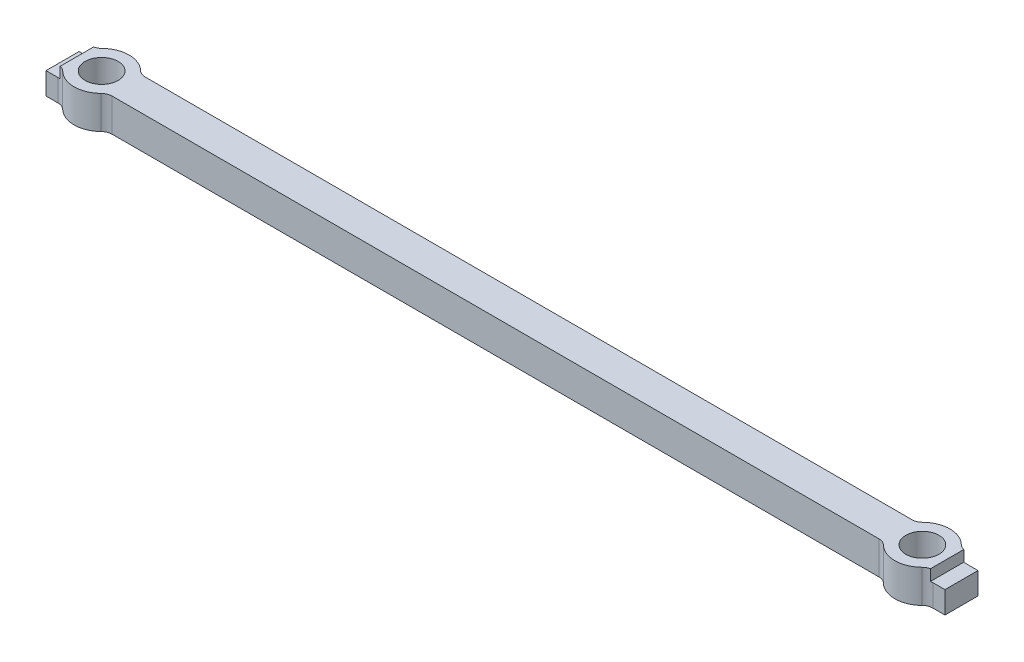
SolidWorks part; units mm, degrees
ref_plane "Front Plane" through (0, 0, 0) normal (0, 0, 1) x (1, 0, 0)
ref_plane "Top Plane" through (0, 0, 0) normal (0, 1, 0) x (1, 0, 0)
ref_plane "Right Plane" through (0, 0, 0) normal (1, 0, 0) x (0, 0, -1)
sketch "Sketch1" plane through (0, 0, 0) normal (0, 1, 0) x (1, 0, 0)
  line L0 (-39.5, 2.5) -> (-39.5, -2.5) construction
  line L1 (-40.8, 2.5) -> (40.8, 2.5)
  line L2 (-40.8, 2.5) -> (-40.8, -2.5)
  line L3 (-40.8, -2.5) -> (40.8, -2.5)
  line L4 (40.8, 2.5) -> (40.8, -2.5)
  line L5 (-40.8, 2.5) -> (40.8, -2.5) construction
  line L6 (-40.8, -2.5) -> (40.8, 2.5) construction
  line L7 (-37.25, 2.5) -> (-37.25, -2.5) construction
  line L8 (-40.8, 0) -> (40.8, 0) construction
  line L9 (0, 2.5) -> (0, -2.5) construction
  line L11 (40.8, 1.5) -> (-40.8, 1.5)
  line L12 (40.8, 1.5) -> (40.8, -1.5)
  line L13 (40.8, -1.5) -> (-40.8, -1.5)
  line L14 (-40.8, 1.5) -> (-40.8, -1.5)
  line L15 (40.8, 1.5) -> (-40.8, -1.5) construction
  line L16 (40.8, -1.5) -> (-40.8, 1.5) construction
  circle A0 centre (-37.25, 0) radius 1.5
  circle A1 centre (-37.25, 0) radius 2.5
  circle A2 centre (37.25, 0) radius 1.5
  circle A3 centre (37.25, 0) radius 2.5
  point P0 (0, 0)
  point P17 (0, 0)
  dimension "D5" = 3
  dimension "D1" = 81.6
  dimension "D2" = 5
  dimension "D3" = 1.3
  dimension "D4" = 2.25
extrude "Shape" add sketch "Sketch1" along normal blind 3 contours L11 A3 L13 L4 | A3 L11 A2 L13 | A3 L13 | A3 L11 | A3 L13 A2 L11 | L13 A3 L11 A1 | L13 A1 L11 A0 | L11 A1 | L11 A1 L13 A0 | A1 L13 | A1 L11 L2 L13 region at (-37.25, 0, -1.9078) region at (-40.1864, 0, 0) region at (37.25, 0, -1.9078) region at (-35.5296, 0, 0) region at (0, 0, 0) region at (-38.9704, 0, 0) region at (38.9704, 0, 0) region at (40.1864, 0, 0) region at (35.5296, 0, 0) region at (-37.25, 0, 1.9078) region at (37.25, 0, 1.9078)
fillet "Mill fillets" radius 1 8 edges at (39.25, 1.5, -1.5) (-35.25, 1.5, -1.5) (-39.25, 1.5, -1.5) (35.25, 1.5, -1.5) (-39.25, 1.5, 1.5) (35.25, 1.5, 1.5) (39.25, 1.5, 1.5) (-35.25, 1.5, 1.5)
sketch "Sketch2" plane through (0, 3, 0) normal (0, 1, 0) x (1, 0, 0)
  line L0 (-39.5, 1.5201) -> (-39.5, -1.5201)
  line L1 (0, 1.5) -> (0, -1.5) construction
  line L2 (39.5, 1.5201) -> (39.5, -1.5201)
  line L8 (34.8005, 1.5) -> (-34.8005, 1.5)
  line L9 (-39.6995, 1.5) -> (-40.8, 1.5)
  line L10 (-40.8, 1.5) -> (-40.8, -1.5)
  line L11 (-40.8, -1.5) -> (-39.6995, -1.5)
  line L12 (-34.8005, -1.5) -> (34.8005, -1.5)
  line L13 (39.6995, -1.5) -> (40.8, -1.5)
  line L14 (40.8, -1.5) -> (40.8, 1.5)
  line L15 (40.8, 1.5) -> (39.6995, 1.5)
  line L16 (34.8005, 1.5) -> (-34.8005, 1.5)
  line L17 (-39.6995, 1.5) -> (-40.8, 1.5)
  line L18 (-40.8, 1.5) -> (-40.8, -1.5)
  line L19 (-40.8, -1.5) -> (-39.6995, -1.5)
  line L20 (-34.8005, -1.5) -> (34.8005, -1.5)
  line L21 (39.6995, -1.5) -> (40.8, -1.5)
  line L22 (40.8, -1.5) -> (40.8, 1.5)
  line L23 (40.8, 1.5) -> (39.6995, 1.5)
  arc A12 (-35.5004, 1.7857) -> (-34.8005, 1.5) centre (-34.8005, 2.5) ccw
  arc A13 (-35.5004, 1.7857) -> (-38.9996, 1.7857) centre (-37.25, 0) ccw
  arc A14 (-39.6995, 1.5) -> (-38.9996, 1.7857) centre (-39.6995, 2.5) ccw
  arc A15 (-38.9996, -1.7857) -> (-39.6995, -1.5) centre (-39.6995, -2.5) ccw
  arc A16 (-38.9996, -1.7857) -> (-35.5004, -1.7857) centre (-37.25, 0) ccw
  arc A17 (-34.8005, -1.5) -> (-35.5004, -1.7857) centre (-34.8005, -2.5) ccw
  arc A18 (35.5004, -1.7857) -> (34.8005, -1.5) centre (34.8005, -2.5) ccw
  arc A19 (35.5004, -1.7857) -> (38.9996, -1.7857) centre (37.25, 0) ccw
  arc A20 (39.6995, -1.5) -> (38.9996, -1.7857) centre (39.6995, -2.5) ccw
  arc A21 (38.9996, 1.7857) -> (39.6995, 1.5) centre (39.6995, 2.5) ccw
  arc A22 (38.9996, 1.7857) -> (35.5004, 1.7857) centre (37.25, 0) ccw
  arc A23 (34.8005, 1.5) -> (35.5004, 1.7857) centre (34.8005, 2.5) ccw
  arc A24 (-35.5004, 1.7857) -> (-34.8005, 1.5) centre (-34.8005, 2.5) ccw
  arc A25 (-35.5004, 1.7857) -> (-38.9996, 1.7857) centre (-37.25, 0) ccw
  arc A26 (-39.6995, 1.5) -> (-38.9996, 1.7857) centre (-39.6995, 2.5) ccw
  arc A27 (-38.9996, -1.7857) -> (-39.6995, -1.5) centre (-39.6995, -2.5) ccw
  arc A28 (-38.9996, -1.7857) -> (-35.5004, -1.7857) centre (-37.25, 0) ccw
  arc A29 (-34.8005, -1.5) -> (-35.5004, -1.7857) centre (-34.8005, -2.5) ccw
  arc A30 (35.5004, -1.7857) -> (34.8005, -1.5) centre (34.8005, -2.5) ccw
  arc A31 (35.5004, -1.7857) -> (38.9996, -1.7857) centre (37.25, 0) ccw
  arc A32 (39.6995, -1.5) -> (38.9996, -1.7857) centre (39.6995, -2.5) ccw
  arc A33 (38.9996, 1.7857) -> (39.6995, 1.5) centre (39.6995, 2.5) ccw
  arc A34 (38.9996, 1.7857) -> (35.5004, 1.7857) centre (37.25, 0) ccw
  arc A35 (34.8005, 1.5) -> (35.5004, 1.7857) centre (34.8005, 2.5) ccw
  arc M26 (-38.9996, 1.7857) -> (-39.6995, 1.5) centre (-39.6995, 2.5) cw
  line M27 (-39.6995, 1.5) -> (-40.8, 1.5)
  line M28 (-40.8, 1.5) -> (-40.8, -1.5)
  line M29 (-40.8, -1.5) -> (-39.6995, -1.5)
  arc M30 (-39.6995, -1.5) -> (-38.9996, -1.7857) centre (-39.6995, -2.5) cw
  arc M36 (38.9996, -1.7857) -> (39.6995, -1.5) centre (39.6995, -2.5) cw
  line M37 (39.6995, -1.5) -> (40.8, -1.5)
  line M38 (40.8, -1.5) -> (40.8, 1.5)
  line M39 (40.8, 1.5) -> (39.6995, 1.5)
  arc M40 (39.6995, 1.5) -> (38.9996, 1.7857) centre (39.6995, 2.5) cw
  dimension "D2" = 1.3
  dimension "D1" = 0
extrude "Edge cuts" cut sketch "Sketch2" against normal offset from surface (1 mm away) 2 contours L0 M26 M27 M28 M29 M30 | L2 M40 M36 M37 M38 M39 region at (-40.1496, 3, 0) region at (40.1496, 3, 0) up to face at (0, 0, 0)
